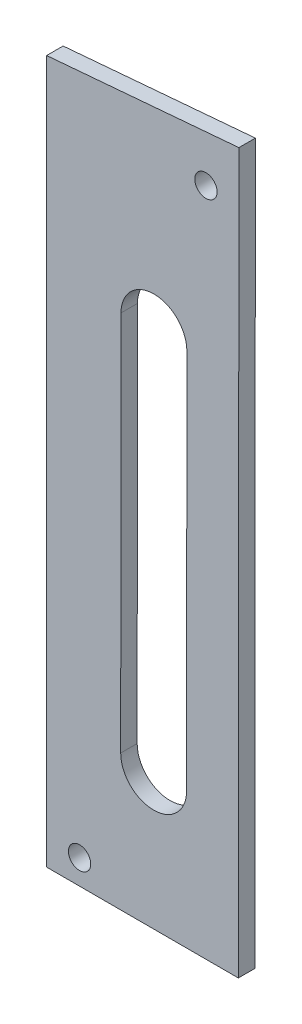
SolidWorks part; units mm, degrees
material "Acrylic (Medium-high impact)"
ref_plane "Front" through (0, 0, 0) normal (0, 0, 1) x (1, 0, 0)
ref_plane "Top" through (0, 0, 0) normal (0, 1, 0) x (1, 0, 0)
ref_plane "Right" through (0, 0, 0) normal (1, 0, 0) x (0, 0, -1)
sketch "Sketch1" plane through (0, 0, 0) normal (0, 0, 1) x (1, 0, 0)
  line L0 (866.1563, 6490.011) -> (829.1993, 6490.0395)
  line L1 (829.1993, 6490.0395) -> (829.1993, 6625.5373)
  line L2 (829.1993, 6625.5373) -> (866.2633, 6628.695)
  line L3 (978.5387, 6638.2603) -> (866.2633, 6628.695) construction
  line L4 (866.2633, 6628.695) -> (866.1563, 6490.011)
  line L5 (849.8832, 6589.7236) -> (849.8265, 6516.2236) construction
  line L6 (846.8832, 6589.7259) -> (852.8832, 6589.7213) construction
  line L7 (852.8265, 6516.2213) -> (846.8265, 6516.2259) construction
  line L8 (856.2332, 6589.7187) -> (856.1765, 6516.2187)
  line L9 (843.5332, 6589.7285) -> (843.4765, 6516.2285)
  arc A0 (856.2332, 6589.7187) -> (843.5332, 6589.7285) centre (849.8832, 6589.7236) ccw
  arc A1 (843.4765, 6516.2285) -> (856.1765, 6516.2187) centre (849.8265, 6516.2236) ccw
  point P14 (849.8548, 6552.9736)
  dimension "D1" = 6.35
extrude "Boss-Extrude1" add sketch "Sketch1" along normal blind 3.175
hole_wizard "#6 Clearance Hole1" positions "Sketch3" profile "Sketch4" hole size "#6" standard "ANSI Inch" end condition through all
sketch "Sketch3" plane through (0, 0, 3.175) normal (0, 0, 1) x (1, 0, 0)
  line L0 (866.1563, 6490.011) -> (866.2633, 6628.695) construction
  line L1 (829.1993, 6490.0395) -> (866.1563, 6490.011) construction
  line L2 (829.1993, 6625.5373) -> (829.1993, 6490.0395) construction
  point P0 (859.906, 6619.1873)
  point P2 (835.5493, 6494.7971)
  dimension "D1" = 6.35
  dimension "D2" = 4.7625
  dimension "D3" = 6.35
  dimension "D4" = 6.35
sketch "Sketch4" plane through (859.906, 6619.1873, 3.175) normal (1, 0, 0) x (0, -1, 0)
  line L0 (0, 0) -> (0, 3.175)
  line L1 (0, 3.175) -> (2.1526, 3.175)
  line L2 (2.1526, 3.175) -> (2.1526, 0)
  line L5 (2.1526, 0) -> (0, 0)
  line L11 (0, -6.35) -> (0, 107.95) construction
  dimension "Thru Hole Dia." = 4.3053
  dimension "Thru Hole Depth" = 3.175
